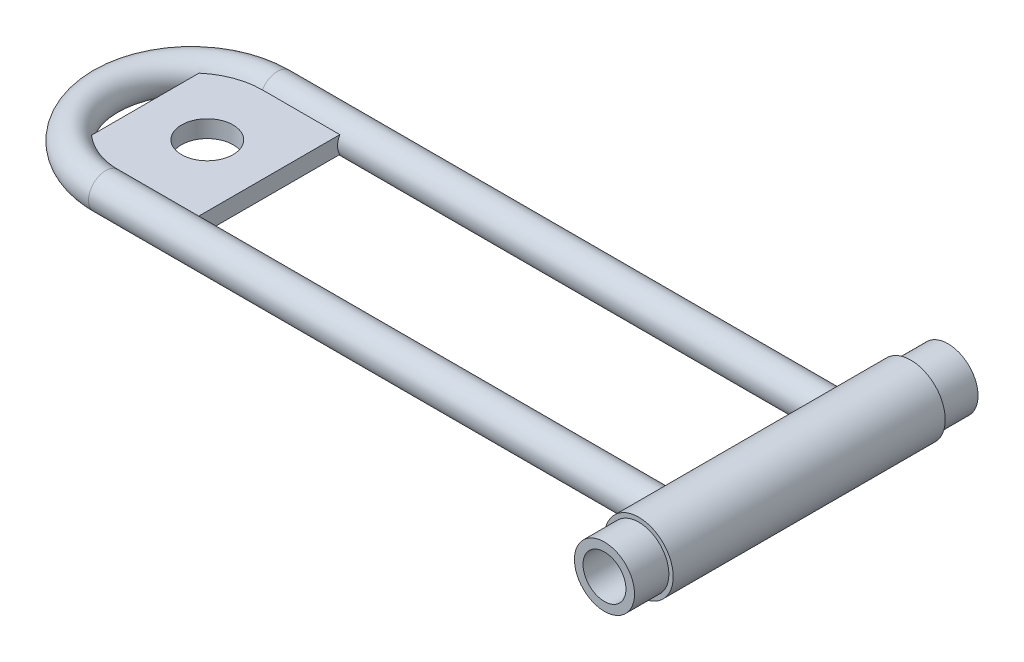
SolidWorks part; units mm, degrees
material "Cast Carbon Steel"
ref_plane "Front Plane" through (0, 0, 0) normal (0, 0, 1) x (1, 0, 0)
ref_plane "Top Plane" through (0, 0, 0) normal (0, 1, 0) x (1, 0, 0)
ref_plane "Right Plane" through (0, 0, 0) normal (1, 0, 0) x (0, 0, -1)
sketch "Sketch1" plane through (0, 0, 0) normal (0, 0, 1) x (1, 0, 0)
  circle A0 centre (0, 0) radius 6.35
  circle A1 centre (0, 0) radius 3.175
  dimension "D1" = 12.7
  dimension "D2" = 3.175
extrude "Boss-Extrude1" add sketch "Sketch1" along normal blind 62.992
ref_plane "Plane1" through (-3.81, 0, 0) normal (-1, 0, 0) x (0, 0, 1)
sketch "Sketch3" plane through (-3.81, 0, 0) normal (-1, 0, 0) x (0, 0, 1)
  line L0 (0, 0) -> (62.992, 0)
  line L1 (62.992, -6.35) -> (62.992, 6.35) construction
  circle A0 centre (-15.748, 0) radius 3.175
  circle A1 centre (47.244, 0) radius 3.175
  dimension "D3" = 6.35
  dimension "D4" = 6.35
  dimension "D1" = 15.748
  dimension "D2" = 15.748
sketch "Sketch4" plane through (0, 0, 0) normal (0, 1, 0) x (1, 0, 0)
  line L0 (-3.81, -15.6639) -> (-107.95, -15.6639)
  line L1 (-3.81, 0) -> (-3.81, -62.992) construction
  line L2 (-3.81, -47.0944) -> (-107.95, -47.0944)
  line L3 (-6.35, 0) -> (-6.35, -62.992) construction
  arc A0 (-107.95, -15.6639) -> (-107.95, -47.0944) centre (-107.95, -31.3792) ccw
  dimension "D1" = 101.6
  dimension "D2" = 15.7152
  dimension "D3" = 31.3792
sweep "Sweep1" add profiles "Sketch3" path "Sketch4"
ref_plane "Plane2" through (0, 0, 15.24) normal (0, 0, 1) x (1, 0, 0)
sketch "Sketch6" plane through (0, 0, 15.24) normal (0, 0, 1) x (1, 0, 0)
  line L0 (-116.5013, 0) -> (-93.6413, 0)
  line L3 (-93.6413, 0) -> (-116.5013, 0)
  line L4 (-93.6413, 0) -> (-93.6413, -1.5875)
  line L5 (-93.6413, -1.5875) -> (-116.5013, -1.5875)
  line L6 (-116.5013, 0) -> (-116.5013, -1.5875)
  line L7 (-93.6413, 0) -> (-116.5013, 0)
  line L8 (-93.6413, 0) -> (-93.6413, 1.5875)
  line L9 (-93.6413, 1.5875) -> (-116.5013, 1.5875)
  line L10 (-116.5013, 0) -> (-116.5013, 1.5875)
  circle A0 centre (0, 0) radius 3.175 construction
  point P3 (-105.0713, 0)
  dimension "D4" = 93.6413
  dimension "D1" = 22.86
  dimension "D2" = 1.5875
  dimension "D3" = 1.5875
extrude "Boss-Extrude3" add sketch "Sketch6" along normal blind 29.21 contours L0 L6 L5 L4 | L10 L0 L8 L9 region at (-105.0713, 0.7937, 15.24) region at (-105.0713, -0.7937, 15.24)
sketch "Sketch7" plane through (0, 1.5875, 0) normal (0, 1, 0) x (1, 0, 0)
  line L1 (-93.6413, -44.45) -> (-93.6413, -18.2639) construction
  circle A0 centre (-105.0713, -31.3411) radius 4.7625
  dimension "D3" = 9.525
  dimension "D1" = 11.43
  dimension "D2" = 9.906
extrude "Cut-Extrude1" cut sketch "Sketch7" against normal blind 29.21
sketch "Sketch9" plane through (0, 0, 0) normal (0, 0, -1) x (-1, 0, 0)
  circle A0 centre (0, 0) radius 6.35
  circle A1 centre (0, 0) radius 3.175
  circle A2 centre (0, 0) radius 6.35 construction
  dimension "D1" = 6.35
  dimension "D2" = 12.7
ref_plane "Plane3" through (0, 0, 31.496) normal (0, 0, 1) x (1, 0, 0)
extrude "Boss-Extrude5" add sketch "Sketch9" along normal blind 6.35
mirror "Mirror1" about plane through (0, 0, 31.496) normal (0, 0, 1) of "Boss-Extrude5"
sketch "Sketch10" plane through (0, 0, 69.342) normal (0, 0, 1) x (1, 0, 0)
  circle A0 centre (0, 0) radius 5.5562
  circle A1 centre (0, 0) radius 6.35
  dimension "D1" = 11.1125
  dimension "D2" = 12.7
extrude "Cut-Extrude6" cut sketch "Sketch10" against normal blind 12.7
sketch "Sketch12" plane through (0, 0, -6.35) normal (0, 0, -1) x (-1, 0, 0)
  circle A0 centre (0, 0) radius 5.5562
  circle A1 centre (0, 0) radius 6.35
  circle A2 centre (0, 0) radius 6.35 construction
  dimension "D1" = 11.1125
  dimension "D2" = 12.7
extrude "Cut-Extrude7" cut sketch "Sketch12" against normal blind 12.7
sketch "Sketch13" plane through (0, 0, 69.342) normal (0, 0, 1) x (1, 0, 0)
  circle A0 centre (0, 0) radius 5.5563
  circle A1 centre (0, 0) radius 3.175
  circle A2 centre (0, 0) radius 3.175 construction
  dimension "D1" = 6.35
  dimension "D2" = 11.1125
extrude "Cut-Extrude8" cut sketch "Sketch13" against normal blind 6.35
sketch "Sketch14" plane through (0, 0, -6.35) normal (0, 0, -1) x (-1, 0, 0)
  circle A0 centre (0, 0) radius 5.5563
  circle A1 centre (0, 0) radius 3.175
  circle A2 centre (0, 0) radius 3.175 construction
  dimension "D1" = 6.35
  dimension "D2" = 11.1125
extrude "Cut-Extrude9" cut sketch "Sketch14" against normal blind 6.35
sketch "Sketch16" plane through (0, 0, 0) normal (0, 0, -1) x (-1, 0, 0)
  circle A0 centre (0, 0) radius 3.9688
  dimension "D1" = 7.9375
extrude "Cut-Extrude11" cut sketch "Sketch16" against normal through all
sketch "Sketch18" plane through (0, 0, 0) normal (0, 0, -1) x (-1, 0, 0)
  circle A0 centre (0, 0) radius 5.5563
  circle A1 centre (0, 0) radius 3.9688
  circle A2 centre (0, 0) radius 3.9688 construction
  dimension "D1" = 7.9375
  dimension "D2" = 11.1125
extrude "Boss-Extrude7" add sketch "Sketch18" along normal blind 0.508
